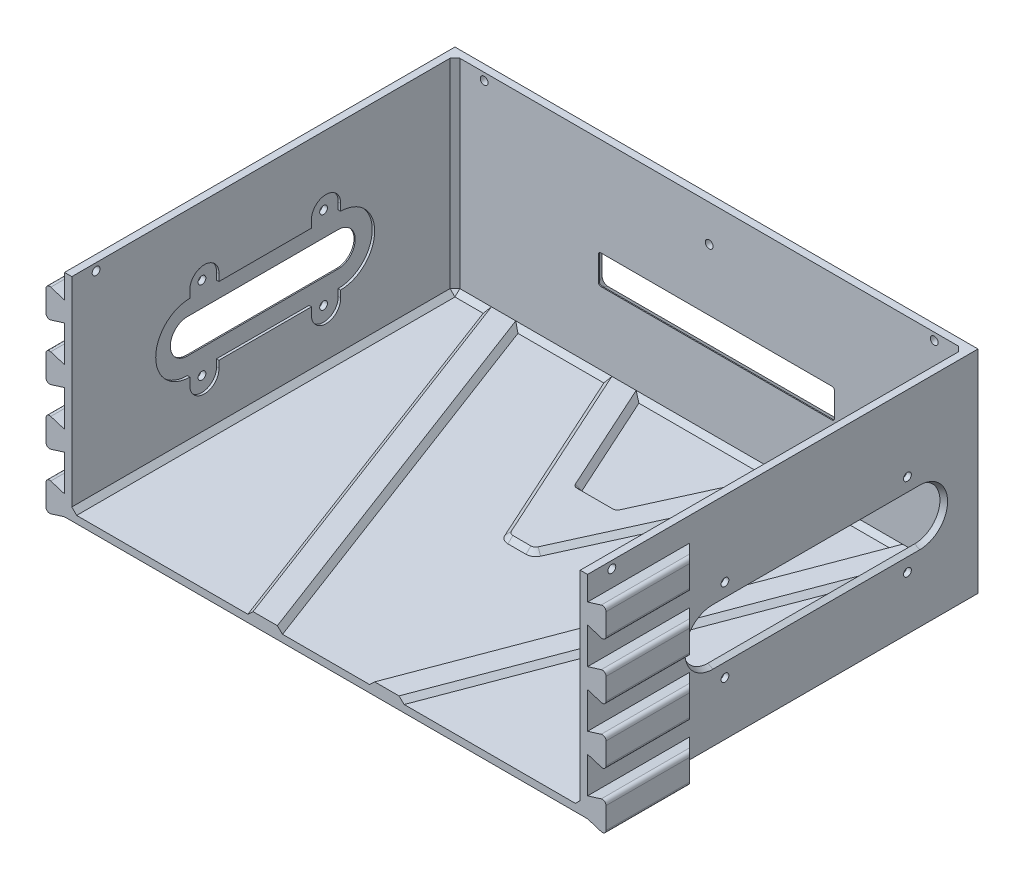
SolidWorks part; units mm, degrees
ref_plane "Płaszczyzna przednia" through (0, 0, 0) normal (0, 0, 1) x (1, 0, 0)
ref_plane "Płaszczyzna górna" through (0, 0, 0) normal (0, 1, 0) x (1, 0, 0)
ref_plane "Płaszczyzna prawa" through (0, 0, 0) normal (1, 0, 0) x (0, 0, -1)
sketch "Szkic1" plane through (0, 0, 0) normal (0, 0, 1) x (1, 0, 0)
  line L1 (0, 0) -> (215, 0)
  line L2 (0, 0) -> (0, 87)
  line L3 (0, 87) -> (215, 87)
  line L4 (215, 0) -> (215, 87)
  dimension "D1" = 87
  dimension "D2" = 215
extrude "Dodanie-wyciągnięcie1" add sketch "Szkic1" along normal blind 3
sketch "Szkic2" plane through (0, 0, 3) normal (0, 0, 1) x (1, 0, 0)
  line L0 (0, 87) -> (0, 0)
  line L1 (0, 0) -> (215, 0)
  line L2 (215, 0) -> (215, 87)
  line L3 (215, 87) -> (212, 87)
  line L4 (215, 87) -> (0, 87) construction
  line L5 (212, 87) -> (212, 3)
  line L6 (212, 3) -> (3, 3)
  line L7 (3, 3) -> (3, 87)
  line L8 (3, 87) -> (0, 87)
  dimension "D1" = 3
  dimension "D2" = 3
  dimension "D3" = 3
extrude "Dodanie-wyciągnięcie2" add sketch "Szkic2" along normal blind 157.5
sketch "Szkic3" plane through (0, 3, 0) normal (0, 1, 0) x (1, 0, 0)
  line L0 (18, -3) -> (77.5, -160.5)
  line L1 (212, -3) -> (3, -3) construction
  line L2 (212, -160.5) -> (3, -160.5) construction
  line L3 (28, -3) -> (87.5, -160.5)
  line L4 (212, -3) -> (3, -3) construction
  line L5 (100.1515, -50) -> (114.8485, -50)
  line L6 (77.5, -160.5) -> (87.5, -160.5)
  line L7 (18, -3) -> (28, -3)
  line L8 (197, -3) -> (137.5, -160.5)
  line L9 (137.5, -160.5) -> (127.5, -160.5)
  line L10 (127.5, -160.5) -> (137.5, -160.5)
  line L11 (127.5, -160.5) -> (187, -3)
  line L12 (187, -3) -> (197, -3)
  line L13 (215, 0) -> (0, 0) construction
  line L14 (67.5, -3) -> (101.9671, -78.8276)
  line L15 (113.0329, -78.8276) -> (147.5, -3)
  line L16 (137.5, -3) -> (116.6693, -48.8276)
  line L17 (98.3307, -48.8276) -> (77.5, -3)
  line L18 (103.7878, -80) -> (111.2122, -80)
  line L19 (67.5, -3) -> (77.5, -3)
  line L20 (137.5, -3) -> (147.5, -3)
  line L21 (107.5, 0) -> (107.5, -100) construction
  arc A0 (114.8485, -50) -> (116.6693, -48.8276) centre (114.8485, -48) ccw
  arc A1 (100.1515, -50) -> (98.3307, -48.8276) centre (100.1515, -48) cw
  arc A2 (111.2122, -80) -> (113.0329, -78.8276) centre (111.2122, -78) ccw
  arc A3 (103.7878, -80) -> (101.9671, -78.8276) centre (103.7878, -78) cw
  point P14 (107.5, 0)
  point P33 (112.5, -80)
  point P36 (102.5, -80)
  point P39 (107.5, -50)
  line M5 (212, -3) -> (3, -3)
  line M7 (3, -160.5) -> (212, -160.5)
  dimension "D16" = 2
  dimension "D1" = 20
  dimension "D2" = 15
  dimension "D3" = 40
  dimension "D4" = 10
  dimension "D5" = 15
  dimension "D6" = 10
  dimension "D7" = 10
  dimension "D8" = 10
  dimension "D9" = 10
  dimension "D10" = 10
  dimension "D11" = 10
  dimension "D12" = 5
  dimension "D13" = 60
  dimension "D14" = 80
  dimension "D15" = 30
extrude "Dodanie-wyciągnięcie3" add sketch "Szkic3" along normal blind 2 contours L3 L0 M5 M7 | L11 L8 M7 M5 | L20 L15 A2 L18 A3 L14 L19 L17 A1 L5 A0 L16 region at (52.75, 3, 81.75) region at (162.25, 3, 81.75)
chamfer "Sfazowanie2" distance 2 angle 45 23 edges at (167.25, 3, 81.75) (212, 45, 3) (212, 3, 81.75) (204.5, 3, 3) (57.75, 3, 81.75) (157.25, 3, 81.75) (167.25, 3, 3) (47.75, 3, 3) (47.75, 3, 81.75) (10.5, 3, 3) (3, 3, 81.75) (3, 45, 3) (107.5, 3, 3) (84.7335, 3, 40.9138) (102.7051, 3, 79.6815) (107.5, 3, 80) (112.2949, 3, 79.6815) (130.2665, 3, 40.9138) (127.0846, 3, 25.9138) (115.9313, 3, 49.6815) (107.5, 3, 50) (99.0687, 3, 49.6815) (87.9154, 3, 25.9138)
sketch "Szkic4" plane through (0, 0, 3) normal (0, 0, 1) x (1, 0, 0)
  line L0 (184.1065, 3) -> (148.7878, 3) construction
  line L1 (63, 46.7) -> (158, 46.7)
  line L2 (62, 45.7) -> (62, 35.7)
  line L3 (63, 34.7) -> (158, 34.7)
  line L4 (159, 45.7) -> (159, 35.7)
  line L5 (212, 87) -> (212, 5) construction
  arc A0 (158, 46.7) -> (159, 45.7) centre (158, 45.7) cw
  arc A1 (158, 34.7) -> (159, 35.7) centre (158, 35.7) ccw
  arc A2 (62, 35.7) -> (63, 34.7) centre (63, 35.7) ccw
  arc A3 (63, 46.7) -> (62, 45.7) centre (63, 45.7) ccw
  point P12 (159, 34.7)
  point P15 (62, 34.7)
  point P18 (62, 46.7)
  dimension "D5" = 1
  dimension "D1" = 31.7
  dimension "D2" = 53
  dimension "D3" = 12
  dimension "D4" = 97
extrude "Wytnij-wyciągnięcie1" cut sketch "Szkic4" against normal blind 10
sketch "Szkic5" plane through (215, 0, 0) normal (1, 0, 0) x (0, 0, -1)
  line L0 (-109, 39) -> (-24, 39) construction
  line L1 (-109, 49) -> (-24, 49)
  line L2 (-109, 29) -> (-24, 29)
  line L3 (-160.5, 0) -> (0, 0) construction
  line L4 (-160.5, 87) -> (0, 87) construction
  line L5 (0, 0) -> (0, 87) construction
  arc A0 (-109, 49) -> (-109, 29) centre (-109, 39) ccw
  arc A1 (-24, 29) -> (-24, 49) centre (-24, 39) ccw
  point P2 (-66.5, 39)
  dimension "D4" = 24
  dimension "D1" = 29
  dimension "D2" = 38
  dimension "D3" = 85
extrude "Wytnij-wyciągnięcie2" cut sketch "Szkic5" against normal blind 10
chamfer "Sfazowanie4" distance 1.5 angle 60 12 edges at (110.5, 46.7, 0) (158.7071, 46.4071, 0) (62.2929, 46.4071, 0) (159, 40.7, 0) (62, 40.7, 0) (158.7071, 34.9929, 0) (62.2929, 34.9929, 0) (110.5, 34.7, 0) (215, 39, 14) (215, 49, 66.5) (215, 29, 66.5) (215, 39, 119) first distance on face at (110.5, 40.7, 0) first distance on face at (215, 39, 66.5)
sketch "Szkic6" plane through (215, 0, 0) normal (1, 0, 0) x (0, 0, -1)
  line L0 (-24, 39) -> (-109, 39) construction
  line L1 (-24, 24) -> (-109, 24)
  line L2 (-24, 54) -> (-109, 54)
  line L3 (-66.5, 39) -> (-66.5, 64.1072) construction
  line L4 (-109, 54) -> (-99, 54)
  line L5 (-109, 54) -> (-109, 56)
  line L7 (-99, 54) -> (-99, 56)
  line L8 (-66.5, 39) -> (-84.4826, 39) construction
  line L9 (-34, 54) -> (-34, 56)
  line L10 (-24, 54) -> (-24, 56)
  line L11 (-24, 54) -> (-34, 54)
  line L12 (-109, 54) -> (-109, 56)
  line L13 (-99, 54) -> (-99, 56)
  line L14 (-34, 54) -> (-34, 56)
  line L15 (-24, 54) -> (-24, 56)
  line L16 (-109, 54) -> (-109, 56)
  line L17 (-99, 54) -> (-99, 56)
  line L18 (-34, 54) -> (-34, 56)
  line L19 (-24, 54) -> (-24, 56)
  line L20 (-109, 54) -> (-109, 56)
  line L21 (-99, 54) -> (-99, 56)
  line L22 (-34, 54) -> (-34, 56)
  line L23 (-24, 54) -> (-24, 56)
  line L24 (-66.5, 39) -> (-132.3508, 39) construction
  line L25 (-109, 54) -> (-109, 56)
  line L26 (-99, 54) -> (-99, 56)
  line L27 (-34, 54) -> (-34, 56)
  line L28 (-24, 54) -> (-24, 56)
  line L29 (-109, 54) -> (-109, 56)
  line L30 (-99, 54) -> (-99, 56)
  line L31 (-34, 54) -> (-34, 56)
  line L32 (-24, 54) -> (-24, 56)
  line L33 (-109, 54) -> (-109, 56)
  line L34 (-99, 54) -> (-99, 56)
  line L35 (-34, 54) -> (-34, 56)
  line L36 (-24, 54) -> (-24, 56)
  line L37 (-109, 54) -> (-109, 56)
  line L38 (-99, 54) -> (-99, 56)
  line L39 (-34, 54) -> (-34, 56)
  line L40 (-24, 54) -> (-24, 56)
  line L41 (-24, 24) -> (-24, 22)
  line L42 (-34, 24) -> (-34, 22)
  line L43 (-109, 24) -> (-109, 22)
  line L44 (-99, 24) -> (-99, 22)
  arc A0 (-24, 24) -> (-24, 54) centre (-24, 39) ccw
  arc A1 (-109, 54) -> (-109, 24) centre (-109, 39) ccw
  arc A2 (-99, 56) -> (-109, 56) centre (-104, 56) ccw
  arc A3 (-34, 56) -> (-24, 56) centre (-29, 56) cw
  arc A4 (-99, 56) -> (-109, 56) centre (-104, 56) ccw
  arc A5 (-34, 56) -> (-24, 56) centre (-29, 56) cw
  arc A6 (-99, 56) -> (-109, 56) centre (-104, 56) ccw
  arc A7 (-34, 56) -> (-24, 56) centre (-29, 56) cw
  arc A8 (-99, 56) -> (-109, 56) centre (-104, 56) ccw
  arc A9 (-34, 56) -> (-24, 56) centre (-29, 56) cw
  arc A10 (-99, 56) -> (-109, 56) centre (-104, 56) ccw
  arc A11 (-34, 56) -> (-24, 56) centre (-29, 56) cw
  arc A12 (-99, 56) -> (-109, 56) centre (-104, 56) ccw
  arc A13 (-34, 56) -> (-24, 56) centre (-29, 56) cw
  arc A14 (-99, 56) -> (-109, 56) centre (-104, 56) ccw
  arc A15 (-34, 56) -> (-24, 56) centre (-29, 56) cw
  arc A16 (-99, 56) -> (-109, 56) centre (-104, 56) ccw
  arc A17 (-34, 56) -> (-24, 56) centre (-29, 56) cw
  arc A18 (-34, 22) -> (-24, 22) centre (-29, 22) ccw
  arc A19 (-99, 22) -> (-109, 22) centre (-104, 22) cw
  point P4 (-66.5, 39)
  line M16 (-109, 50.5) -> (-24, 50.5)
  arc M17 (-24, 50.5) -> (-24, 27.5) centre (-24, 39) cw
  line M18 (-24, 27.5) -> (-109, 27.5)
  arc M19 (-109, 27.5) -> (-109, 50.5) centre (-109, 39) cw
  dimension "D1" = 15
  dimension "D3" = 5
  dimension "D2" = 10
  dimension "D4" = 2
extrude "Wytnij-wyciągnięcie3" cut sketch "Szkic6" along normal blind 1 from surface contours A19 L44 L1 L43 | L42 A18 L41 L1 | L2 A1 L1 A0 M19 M16 M17 M18 | A3 L9 L2 L10 | L7 A2 L5 L2 | M16 M19 M18 M17 region at (215, 20.9314, 29) region at (215, 25.1885, 29) region at (215, 57.0686, 29) region at (215, 20.9314, 104) region at (215, 57.0686, 104) region at (215, 39, 66.5) starting at face at (212, 39, 66.5)
sketch "Szkic7" plane through (215, 0, 0) normal (1, 0, 0) x (0, 0, -1)
  line L0 (-66.5, 39) -> (-66.5, 73.0963) construction
  line L1 (-66.5, 39) -> (-141.7626, 39) construction
  circle A0 centre (-104, 56) radius 1.6
  circle A1 centre (-29, 56) radius 1.6
  circle A2 centre (-29, 22) radius 1.6
  circle A3 centre (-104, 22) radius 1.6
  dimension "D1" = 3.2
extrude "Wytnij-wyciągnięcie4" cut sketch "Szkic7" against normal blind 3
sketch "Szkic10" plane through (0, 0, 160.5) normal (0, 0, 1) x (1, 0, 0)
  line L0 (222.6, 87) -> (222.6, 0) construction
  line L1 (215, 0) -> (215, 87) construction
  line L2 (215, 0) -> (215, 8.16)
  line L3 (215, 0) -> (220.6526, -1.7665)
  line L4 (215, 8.16) -> (220.6526, 9.9265)
  line L5 (222.6, 8.4948) -> (222.6, -0.3348)
  line L6 (107.5, 87) -> (107.5, 114.4452) construction
  line L7 (210, 87) -> (5, 87) construction
  line L8 (215, 23) -> (215, 31.16)
  line L9 (215, 23) -> (220.6526, 21.2335)
  line L10 (215, 31.16) -> (220.6526, 32.9265)
  line L11 (222.6, 31.4948) -> (222.6, 22.6652)
  line L12 (215, 46) -> (215, 54.16)
  line L13 (215, 46) -> (220.6526, 44.2335)
  line L14 (215, 54.16) -> (220.6526, 55.9265)
  line L15 (222.6, 54.4948) -> (222.6, 45.6652)
  line L16 (-7.6, 54.4948) -> (-7.6, 45.6652)
  line L17 (0, 54.16) -> (-5.6526, 55.9265)
  line L18 (0, 46) -> (-5.6526, 44.2335)
  line L19 (0, 46) -> (0, 54.16)
  line L20 (-7.6, 31.4948) -> (-7.6, 22.6652)
  line L21 (0, 31.16) -> (-5.6526, 32.9265)
  line L22 (0, 23) -> (-5.6526, 21.2335)
  line L23 (0, 23) -> (0, 31.16)
  line L24 (-7.6, 8.4948) -> (-7.6, -0.3348)
  line L25 (0, 8.16) -> (-5.6526, 9.9265)
  line L26 (0, 0) -> (-5.6526, -1.7665)
  line L27 (0, 0) -> (0, 8.16)
  line L28 (215, 69) -> (215, 77.16)
  line L29 (215, 69) -> (220.6526, 67.2335)
  line L30 (215, 77.16) -> (220.6526, 78.9265)
  line L31 (222.6, 77.4948) -> (222.6, 68.6652)
  line L32 (-7.6, 77.4948) -> (-7.6, 68.6652)
  line L33 (0, 77.16) -> (-5.6526, 78.9265)
  line L34 (0, 69) -> (-5.6526, 67.2335)
  line L35 (0, 69) -> (0, 77.16)
  arc A0 (220.6526, -1.7665) -> (222.6, -0.3348) centre (221.1, -0.3348) ccw
  arc A1 (220.6526, 9.9265) -> (222.6, 8.4948) centre (221.1, 8.4948) cw
  arc A2 (220.6526, 21.2335) -> (222.6, 22.6652) centre (221.1, 22.6652) ccw
  arc A3 (220.6526, 32.9265) -> (222.6, 31.4948) centre (221.1, 31.4948) cw
  arc A4 (220.6526, 44.2335) -> (222.6, 45.6652) centre (221.1, 45.6652) ccw
  arc A5 (220.6526, 55.9265) -> (222.6, 54.4948) centre (221.1, 54.4948) cw
  arc A6 (-5.6526, 55.9265) -> (-7.6, 54.4948) centre (-6.1, 54.4948) ccw
  arc A7 (-5.6526, 44.2335) -> (-7.6, 45.6652) centre (-6.1, 45.6652) cw
  arc A8 (-5.6526, 32.9265) -> (-7.6, 31.4948) centre (-6.1, 31.4948) ccw
  arc A9 (-5.6526, 21.2335) -> (-7.6, 22.6652) centre (-6.1, 22.6652) cw
  arc A10 (-5.6526, 9.9265) -> (-7.6, 8.4948) centre (-6.1, 8.4948) ccw
  arc A11 (-5.6526, -1.7665) -> (-7.6, -0.3348) centre (-6.1, -0.3348) cw
  arc A12 (220.6526, 67.2335) -> (222.6, 68.6652) centre (221.1, 68.6652) ccw
  arc A13 (220.6526, 78.9265) -> (222.6, 77.4948) centre (221.1, 77.4948) cw
  arc A14 (-5.6526, 78.9265) -> (-7.6, 77.4948) centre (-6.1, 77.4948) ccw
  arc A15 (-5.6526, 67.2335) -> (-7.6, 68.6652) centre (-6.1, 68.6652) cw
  point P11 (222.6, -2.3751)
  point P14 (222.6, 10.5351)
  point P37 (0, 0)
  point P60 (-7.6, 10.5351)
  point P61 (-7.6, -2.3751)
  dimension "D5" = 1.5
  dimension "D1" = 7.6
  dimension "D2" = 8.16
  dimension "D3" = 23
  dimension "D4" = 34.71
  dimension "D6" = 3
extrude "Dodanie-wyciągnięcie6" add sketch "Szkic10" against normal blind 32
chamfer "Sfazowanie5" distance 10 angle 45 6 edges at (215, 50.08, 128.5) (215, 4.08, 128.5) (0, 4.08, 128.5) (215, 27.08, 128.5) (215, 73.08, 128.5) (0, 73.08, 128.5)
sketch "Szkic11" plane through (0, 0, 0) normal (-1, 0, 0) x (0, 0, 1)
  line L0 (112, 41) -> (50, 41) construction
  line L1 (112, 34) -> (50, 34)
  line L2 (112, 48) -> (50, 48)
  line L3 (160.5, 87) -> (0, 87) construction
  line L4 (0, 87) -> (0, 0) construction
  arc A0 (112, 34) -> (112, 48) centre (112, 41) ccw
  arc A1 (50, 48) -> (50, 34) centre (50, 41) ccw
  point P2 (81, 41)
  dimension "D3" = 7
  dimension "D1" = 39
  dimension "D2" = 62
  dimension "D4" = 50
extrude "Wytnij-wyciągnięcie5" cut sketch "Szkic11" against normal blind 10
sketch "Szkic12" plane through (0, 0, 0) normal (-1, 0, 0) x (0, 0, 1)
  line L0 (112, 41) -> (50, 41) construction
  line L1 (112, 27) -> (50, 27)
  line L2 (112, 55) -> (50, 55)
  line L3 (102.8467, 55) -> (100, 55)
  line L4 (112, 55) -> (102.8467, 55)
  line L5 (112, 55) -> (112, 57.7839)
  line L7 (100, 55) -> (100, 57.7839)
  line L8 (81, 41) -> (81, 27) construction
  line L9 (62, 55) -> (62, 57.7839)
  line L10 (50, 55) -> (50, 57.7839)
  line L11 (50, 55) -> (59.1533, 55)
  line L12 (59.1533, 55) -> (62, 55)
  line L13 (81, 41) -> (24.5654, 41) construction
  line L14 (59.1533, 27) -> (62, 27)
  line L15 (50, 27) -> (59.1533, 27)
  line L16 (50, 27) -> (50, 24.2161)
  line L17 (62, 27) -> (62, 24.2161)
  line L18 (100, 27) -> (100, 24.2161)
  line L19 (112, 27) -> (112, 24.2161)
  line L20 (112, 27) -> (102.8467, 27)
  line L21 (102.8467, 27) -> (100, 27)
  arc A0 (112, 27) -> (112, 55) centre (112, 41) ccw
  arc A1 (50, 55) -> (50, 27) centre (50, 41) ccw
  arc A2 (112, 57.7839) -> (100, 57.7839) centre (106, 58) ccw
  arc A3 (50, 57.7839) -> (62, 57.7839) centre (56, 58) cw
  arc A4 (50, 24.2161) -> (62, 24.2161) centre (56, 24) ccw
  arc A5 (112, 24.2161) -> (100, 24.2161) centre (106, 24) cw
  point P4 (81, 41)
  line M18 (50, 48) -> (112, 48)
  arc M19 (112, 48) -> (112, 34) centre (112, 41) cw
  line M20 (112, 34) -> (50, 34)
  arc M21 (50, 34) -> (50, 48) centre (50, 41) cw
  line M22 (118.5, 0) -> (118.5, 8.16)
  line M23 (118.5, 8.16) -> (160.5, 8.16)
  dimension "D2" = 14
  dimension "D1" = 12
  dimension "D3" = 34
extrude "Wytnij-wyciągnięcie6" cut sketch "Szkic12" along normal blind 1 from surface contours L2 A1 L1 A0 M21 M18 M19 M20 | L5 A2 L7 L2 | A5 L19 L1 L18 M22 M23 | L16 A4 L17 L1 | A3 L10 L2 L9 region at (0, 23.0253, 106) region at (0, 27.9425, 107.4233) region at (0, 58.9747, 106) region at (0, 23.0253, 56) region at (0, 58.9747, 56) starting at face at (3, 41, 81)
sketch "Szkic13" plane through (0, 0, 0) normal (-1, 0, 0) x (0, 0, 1)
  line L0 (81, 41) -> (81, 27) construction
  line L1 (112, 41) -> (50, 41) construction
  line L4 (24.5654, 41) -> (81, 41) construction
  circle A0 centre (106, 58) radius 1.6
  circle A1 centre (106, 24) radius 1.6
  circle A2 centre (56, 24) radius 1.6
  circle A3 centre (56, 58) radius 1.6
  dimension "D1" = 3.2
extrude "Wytnij-wyciągnięcie7" cut sketch "Szkic13" against normal blind 3
chamfer "Sfazowanie8" distance 1.5 angle 60 4 edges at (0, 48, 81) (0, 41, 43) (0, 41, 119) (0, 34, 81) first distance on face at (1, 48, 81) first distance on face at (1, 41, 46.5) first distance on face at (1, 41, 115.5) first distance on face at (1, 34, 81)
sketch "Szkic14" plane through (0, 0, 0) normal (-1, 0, 0) x (0, 0, 1)
  line L0 (160.5, 87) -> (160.5, 77.16) construction
  line L1 (160.5, 87) -> (0, 87) construction
  circle A0 centre (150.5, 84) radius 1.6
  dimension "D2" = 3.2
  dimension "D1" = 10
  dimension "D3" = 3
extrude "Wytnij-wyciągnięcie8" cut sketch "Szkic14" against normal through all
sketch "Szkic15" plane through (0, 0, 0) normal (0, 0, -1) x (-1, 0, 0)
  line L0 (0, 87) -> (0, 0) construction
  line L1 (-215, 87) -> (0, 87) construction
  circle A0 centre (-15, 84) radius 1.6
  dimension "D1" = 3.2
  dimension "D2" = 15
  dimension "D3" = 3
extrude "Wytnij-wyciągnięcie9" cut sketch "Szkic15" against normal through all contours A0
ref_plane "Płaszczyzna1" through (107.5, 0, 0) normal (-1, 0, 0) x (0, 0, 1)
mirror "Lustro1" about plane through (107.5, 0, 0) normal (-1, 0, 0) of "Wytnij-wyciągnięcie9"
sketch "Szkic16" plane through (0, 0, 0) normal (0, 0, -1) x (-1, 0, 0)
  line L0 (-107.5, -47.85) -> (-107.5, 47.85) construction
  line L1 (-215, 87) -> (0, 87) construction
  circle A0 centre (-107.5, 72) radius 1.6
  dimension "D1" = 3.2
  dimension "D2" = 15
extrude "Wytnij-wyciągnięcie10" cut sketch "Szkic16" against normal blind 35
